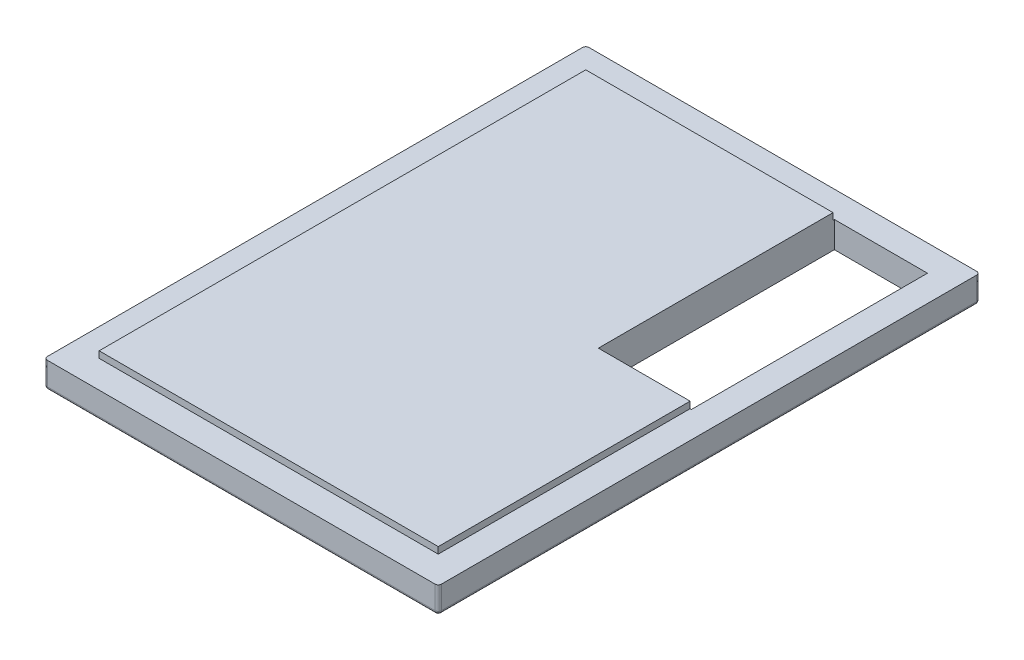
SolidWorks part; units mm, degrees
ref_plane "Front" through (0, 0, 0) normal (0, 0, 1) x (1, 0, 0)
ref_plane "Top" through (0, 0, 0) normal (0, 1, 0) x (1, 0, 0)
ref_plane "Right" through (0, 0, 0) normal (1, 0, 0) x (0, 0, -1)
sketch "Sketch1" plane through (0, 0, 0) normal (0, 1, 0) x (1, 0, 0)
  line L1 (-15.03, -20.655) -> (15.03, -20.655)
  line L2 (-15.03, -20.655) -> (-15.03, 20.655)
  line L3 (-15.03, 20.655) -> (15.03, 20.655)
  line L4 (15.03, -20.655) -> (15.03, 20.655)
  line L5 (-15.03, -20.655) -> (15.03, 20.655) construction
  line L6 (-15.03, 20.655) -> (15.03, -20.655) construction
  point P0 (0, 0)
  dimension "D1" = 30.06
  dimension "D2" = 41.31
extrude "Boss-Extrude1" add sketch "Sketch1" along normal blind 2.5
sketch "Sketch2" plane through (0, 2.5, 0) normal (0, 1, 0) x (1, 0, 0)
  line L8 (12.93, -18.555) -> (12.93, 18.555)
  line L9 (12.93, 18.555) -> (-12.93, 18.555)
  line L10 (-12.93, 18.555) -> (-12.93, -18.555)
  line L11 (-12.93, -18.555) -> (12.93, -18.555)
  line L12 (12.93, -18.555) -> (12.93, 18.555)
  line L13 (12.93, 18.555) -> (-12.93, 18.555)
  line L14 (-12.93, 18.555) -> (-12.93, -18.555)
  line L15 (-12.93, -18.555) -> (12.93, -18.555)
  dimension "D1" = 2.1
extrude "Cut-Extrude1" cut sketch "Sketch2" against normal blind 0.5 flip side to cut
fillet "Fillet1" radius 0.25 8 edges at (0, 0, -20.655) (-15.03, 1, -20.655) (-15.03, 0, 0) (15.03, 0, 0) (0, 0, 20.655) (-15.03, 1, 20.655) (15.03, 1, 20.655) (15.03, 1, -20.655)
sketch "Sketch4" plane through (0, 0, 0) normal (0, -1, 0) x (-1, 0, 0)
  line L0 (-15.03, 20.655) -> (14.78, 20.655) construction
  line L1 (-13.03, 18.655) -> (-5.93, 18.655)
  line L2 (-13.03, 18.655) -> (-13.03, 0.655)
  line L3 (-13.03, 0.655) -> (-5.93, 0.655)
  line L4 (-5.93, 18.655) -> (-5.93, 0.655)
  line L5 (-15.03, -20.405) -> (-15.03, 20.655) construction
  dimension "D1" = 2
  dimension "D2" = 2
  dimension "D3" = 7.1
  dimension "D4" = 18
extrude "Cut-Extrude3" cut sketch "Sketch4" against normal through all
